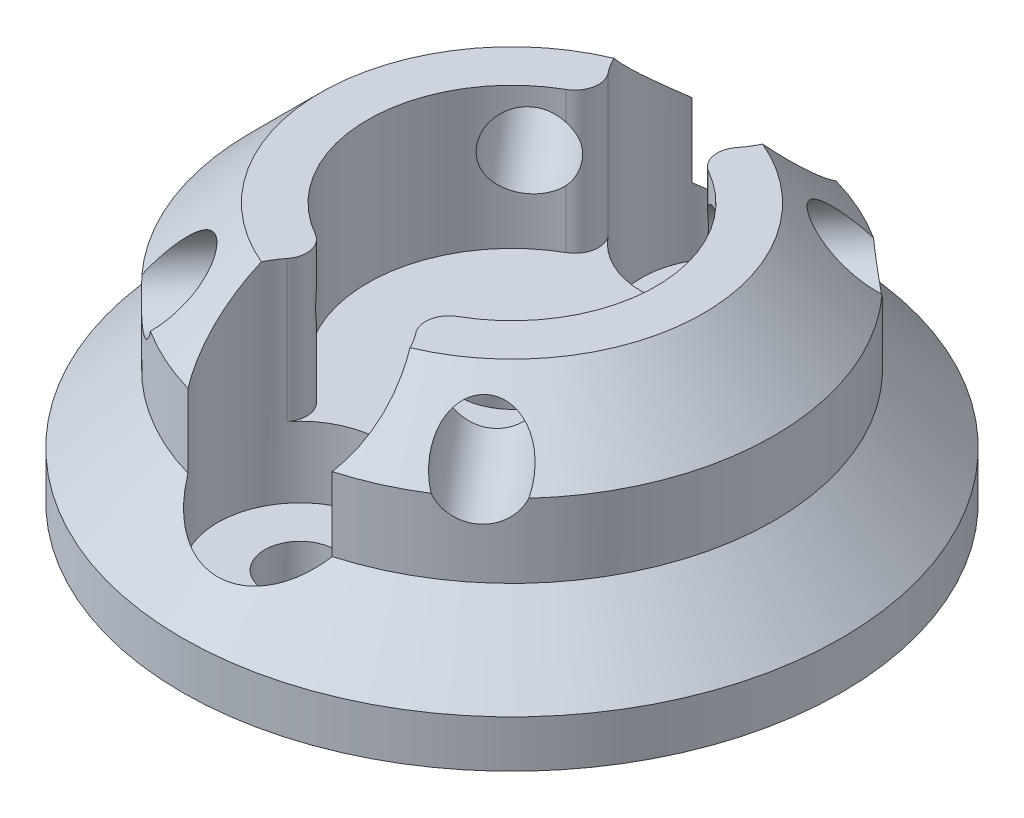
SolidWorks part; units mm, degrees
ref_plane "Front Plane" through (0, 0, 0) normal (0, 0, 1) x (1, 0, 0)
ref_plane "Top Plane" through (0, 0, 0) normal (0, 1, 0) x (1, 0, 0)
ref_plane "Right Plane" through (0, 0, 0) normal (1, 0, 0) x (0, 0, -1)
sketch "Sketch1" plane through (0, 0, 0) normal (0, 1, 0) x (1, 0, 0)
  circle A0 centre (0, 0) radius 14
  circle A1 centre (0, 0) radius 2.25
  dimension "D1" = 28
  dimension "D2" = 4.5
extrude "Boss-Extrude1" add sketch "Sketch1" along normal blind 5
sketch "Sketch2" plane through (0, 5, 0) normal (0, 1, 0) x (1, 0, 0)
  line L0 (0, -1000) -> (0, 49000) construction
  line L1 (-1000, 0) -> (49000, 0) construction
  line L2 (4.2426, 4.2426) -> (0, 0) construction
  circle A0 centre (0, 9) radius 1.5
  circle A1 centre (4.2426, 4.2426) radius 1.5 construction
  dimension "D1" = 3
  dimension "D2" = 3
  dimension "D3" = 9
  dimension "D4" = 6
  dimension "D5" = 45
extrude "Cut-Extrude1" cut sketch "Sketch2" against normal through all
sketch "Sketch4" plane through (0, 5, 0) normal (0, 1, 0) x (1, 0, 0)
  circle A0 centre (0, 9) radius 3.5
  dimension "D1" = 7
extrude "Cut-Extrude2" cut sketch "Sketch4" against normal blind 3
pattern_circular "CirPattern1" count 2 over 360 about axis through (0, 5, 0) along (0, -1, 0) of "Cut-Extrude1", "Cut-Extrude2" reverse direction yes
sketch "Sketch5" plane through (0, 5, 0) normal (0, 1, 0) x (1, 0, 0)
  circle A0 centre (0, 0) radius 6.125
  circle A1 centre (0, 0) radius 11.125
  dimension "D1" = 12.25
  dimension "D2" = 5
extrude "Boss-Extrude2" add sketch "Sketch5" along normal blind 6
sketch "Sketch6" plane through (0, 5, 0) normal (0, 1, 0) x (1, 0, 0)
  circle A2 centre (0, 9) radius 3.5 construction
  circle A3 centre (0, -9) radius 3.5 construction
  circle A6 centre (0, 9) radius 3.5
  circle A7 centre (0, -9) radius 3.5
extrude "Cut-Extrude3" cut sketch "Sketch6" along normal through all
chamfer "Chamfer1" distance 3 angle 45 1 edges at (0, 5, 14)
fillet "Fillet1" radius 1 4 edges at (1.6317, 8, 5.9036) (-1.6317, 8, 5.9036) (1.6317, 8, -5.9036) (-1.6317, 8, -5.9036)
ref_axis "Axis1" through (0, 11, 0) along (0, -1, 0)
ref_plane "Plane1" through (0, 0, 0) normal (-0.6428, 0, 0.766) x (0, -1, 0)
sketch "Sketch8" plane through (0, 0, 0) normal (-0.6428, 0, 0.766) x (0, -1, 0)
  line L0 (-11, 0) -> (-5, 0) construction
  line L2 (-4.875, -11.125) -> (-4.875, 4.5292) construction
  circle A0 centre (-8.625, 0) radius 1.6
  point P2 (0, 0)
  point P3 (0, 0)
  point P5 (-7.3631, 0)
  dimension "D1" = 3.2
  dimension "D2" = 3.75
extrude "Cut-Extrude4" cut sketch "Sketch8" against normal through all and the other way through all
chamfer "Chamfer2" distance 3 angle 45 2 edges at (11.125, 11, 0) (-11.125, 11, 0)
pattern_circular "CirPattern2" count 2 every 100 about axis through (0, 5, 0) along (0, -1, 0) of "Cut-Extrude4"
